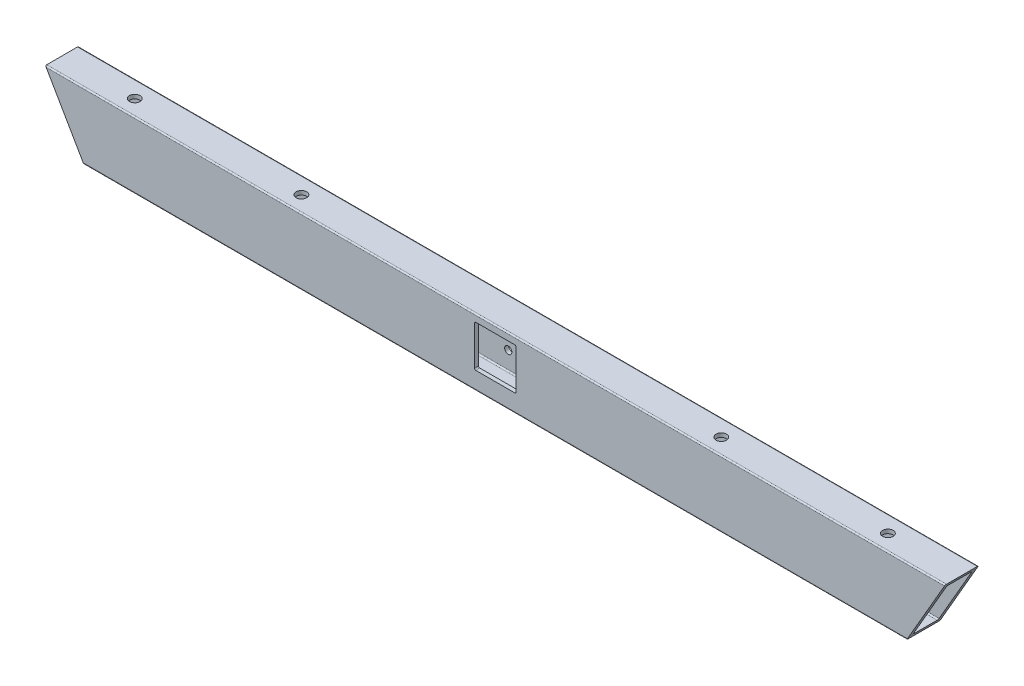
SolidWorks part; units mm, degrees
ref_plane "Front Plane" through (0, 0, 0) normal (0, 0, 1) x (1, 0, 0)
ref_plane "Top Plane" through (0, 0, 0) normal (0, 1, 0) x (1, 0, 0)
ref_plane "Right Plane" through (0, 0, 0) normal (1, 0, 0) x (0, 0, -1)
sketch "Sketch2" plane through (0, 0, 0) normal (0, 0, 1) x (1, 0, 0)
  line L0 (-313.5706, -25.4) -> (-342.9, 25.4)
  line L1 (-342.9, 25.4) -> (342.9, 25.4)
  line L3 (-313.5706, -25.4) -> (313.5706, -25.4)
  line L5 (0, 25.4) -> (0, -25.4) construction
  line L8 (313.5706, -25.4) -> (342.9, 25.4)
  point P0 (0, 0)
  point P4 (0, 0)
  point P8 (0, 25.4)
  dimension "D1" = 50.8
  dimension "D2" = 60
  dimension "D3" = 685.8
extrude "Boss-Extrude1" add sketch "Sketch2" along normal mid plane 25.4 contours L1 L8 L3 L0
sketch "Sketch3" plane through (0, 0, 0) normal (1, 0, 0) x (0, 0, -1)
  line L12 (9.652, -22.352) -> (9.652, 22.352)
  line L13 (-9.652, -22.352) -> (9.652, -22.352)
  line L14 (-9.652, 22.352) -> (-9.652, -22.352)
  line L15 (9.652, 22.352) -> (-9.652, 22.352)
  line L16 (9.652, -22.352) -> (9.652, 22.352)
  line L17 (-9.652, -22.352) -> (9.652, -22.352)
  line L18 (-9.652, 22.352) -> (-9.652, -22.352)
  line L19 (9.652, 22.352) -> (-9.652, 22.352)
  dimension "D1" = 3.048
extrude "Cut-Extrude1" cut sketch "Sketch3" against normal through all and the other way through all contours L16 L19 L18 L17
fillet "Fillet1" radius 1 8 edges at (0, 22.352, 9.652) (0, 22.352, -9.652) (0, -22.352, -9.652) (0, -22.352, 9.652) (0, -25.4, -12.7) (0, -25.4, 12.7) (0, 25.4, -12.7) (0, 25.4, 12.7)
sketch "Sketch4" plane through (0, 0, -12.7) normal (0, 0, -1) x (-1, 0, 0)
  line L1 (7, 0) -> (7, 10)
  line L2 (-7, 0) -> (-7, 10)
  arc A0 (-7, 0) -> (7, 0) centre (0, 0) ccw
  arc A1 (7, 10) -> (-7, 10) centre (0, 10) ccw
  dimension "D1" = 14
  dimension "D2" = 10
extrude "Cut-Extrude2" cut sketch "Sketch4" against normal up to next
sketch "Sketch5" plane through (0, 0, 12.7) normal (0, 0, 1) x (1, 0, 0)
  line L0 (15.875, 4) -> (-15.875, 4) construction
  line L1 (14.875, -11.875) -> (-14.875, -11.875)
  line L2 (15.875, -10.875) -> (15.875, 18.875)
  line L3 (14.875, 19.875) -> (-14.875, 19.875)
  line L4 (-15.875, -10.875) -> (-15.875, 18.875)
  arc A0 (-14.875, -11.875) -> (-15.875, -10.875) centre (-14.875, -10.875) cw
  arc A1 (14.875, -11.875) -> (15.875, -10.875) centre (14.875, -10.875) ccw
  arc A2 (15.875, 18.875) -> (14.875, 19.875) centre (14.875, 18.875) ccw
  arc A3 (-14.875, 19.875) -> (-15.875, 18.875) centre (-14.875, 18.875) ccw
  point P1 (0, 19.875)
  dimension "D2" = 1
  dimension "D1" = 31.75
  dimension "D3" = 4
extrude "Cut-Extrude3" cut sketch "Sketch5" against normal up to next
hole_wizard "M5 Clearance Hole1" positions "Sketch12" profile "Sketch7" hole size "M5" standard "ANSI Metric" end condition up to next
sketch "Sketch12" plane through (0, 0, -9.652) normal (0, 0, 1) x (1, 0, 0)
  line L1 (12.5, 16.5) -> (12.5, -8.5) construction
  line L2 (12.5, -8.5) -> (-12.5, -8.5) construction
  circle A5 centre (-12.5, 16.5) radius 2.1 construction
  point P0 (-12.5, 16.5)
  point P2 (12.5, 16.5)
  point P4 (12.5, -8.5)
  point P6 (-12.5, -8.5)
  point P47 (0, -8.5)
  dimension "D1" = 25
  dimension "D2" = 25
sketch "Sketch7" plane through (-12.5, 16.5, -9.652) normal (1, 0, 0) x (0, -1, 0)
  line L0 (0, 0) -> (0, 3.048)
  line L1 (0, 3.048) -> (2.75, 3.048)
  line L2 (2.75, 3.048) -> (2.75, 0)
  line L5 (2.75, 0) -> (0, 0)
  line L11 (0, -6.35) -> (0, 107.95) construction
  dimension "Thru Hole Dia." = 5.5
  dimension "Thru Hole Depth" = 3.048
sketch "Sketch9" plane through (0, 0, -12.7) normal (0, 0, -1) x (-1, 0, 0)
  line L0 (-222.25, 0) -> (-215.9, 0) construction
  line L1 (-222.25, 7.1437) -> (-215.9, 7.1437)
  line L2 (-222.25, -7.1437) -> (-215.9, -7.1437)
  line L3 (0, 13.97) -> (0, -13.97) construction
  line L4 (222.25, 0) -> (215.9, 0) construction
  line L5 (222.25, 7.1437) -> (215.9, 7.1437)
  line L6 (222.25, -7.1437) -> (215.9, -7.1437)
  arc A0 (-222.25, 7.1437) -> (-222.25, -7.1437) centre (-222.25, 0) ccw
  arc A1 (-215.9, -7.1437) -> (-215.9, 7.1437) centre (-215.9, 0) ccw
  arc A2 (222.25, 7.1437) -> (222.25, -7.1437) centre (222.25, 0) cw
  arc A3 (215.9, -7.1437) -> (215.9, 7.1437) centre (215.9, 0) cw
  point P2 (-219.075, 0)
  point P12 (219.075, 0)
  dimension "D2" = 14.2875
  dimension "D1" = 6.35
  dimension "D3" = 215.9
extrude "Cut-Extrude4" cut sketch "Sketch9" against normal up to next
sketch "Sketch14" plane through (0, 25.4, 0) normal (0, 1, 0) x (1, 0, 0)
  line L0 (-159.9992, -0.5) -> (-286.9992, -0.5) construction
  line L1 (342.3226, -12.7) -> (-342.3226, -12.7) construction
  line L3 (159.9992, -0.5) -> (286.9992, -0.5) construction
  line L4 (0, 0) -> (0, 11.7) construction
  line L5 (342.9, 11.7) -> (-342.9, 11.7) construction
  circle A0 centre (-159.9992, -0.5) radius 4
  circle A2 centre (-286.9992, -0.5) radius 4
  circle A6 centre (286.9992, -0.5) radius 4
  circle A7 centre (159.9992, -0.5) radius 4
  dimension "D1" = 8
  dimension "D2" = 160
  dimension "D3" = 127
extrude "Cut-Extrude7" cut sketch "Sketch14" against normal up to next
mirror "Mirror1" [suppressed] of bodies 110 106
sketch "Sketch10" [suppressed] plane through (0, 0, 0) normal (1, 0, 0) x (0, 0, -1)
  line L0 (-12.7, -24.4) -> (-12.7, 24.4) construction
  line L1 (12.7, -25.4) -> (-12.7, -25.4)
  line L2 (12.7, -25.4) -> (12.7, 25.4)
  line L3 (12.7, 25.4) -> (-12.7, 25.4)
  line L4 (-12.7, -25.4) -> (-12.7, 25.4)
  line L5 (12.7, -25.4) -> (-12.7, 25.4) construction
  line L6 (12.7, 25.4) -> (-12.7, -25.4) construction
  line L7 (-11.7, 25.4) -> (11.7, 25.4) construction
  point P0 (0, 0)
extrude "Cut-Extrude5" [suppressed] cut sketch "Sketch10" against normal through all both and the other way through all
sketch "Sketch13" [suppressed] plane through (0, 0, -38.1) normal (0, 0, -1) x (-1, 0, 0)
  circle A0 centre (241.3, 0) radius 7.5
  dimension "D1" = 15
  dimension "D2" = 241.3
extrude "Cut-Extrude6" [suppressed] cut sketch "Sketch13" against normal up to next
